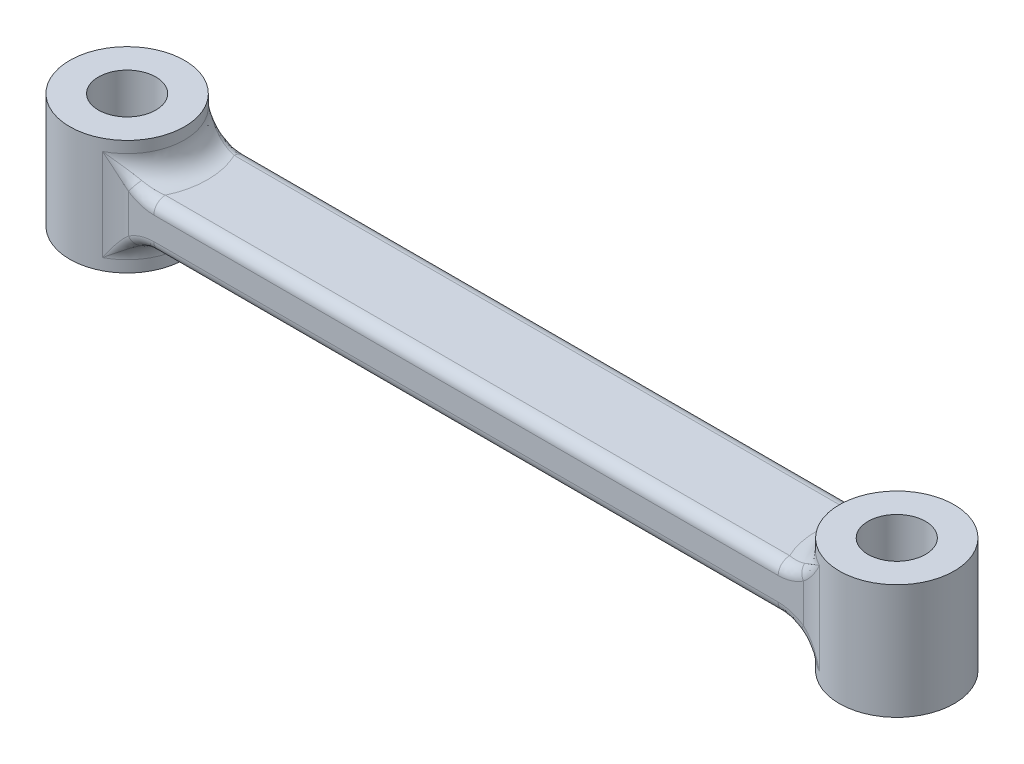
SolidWorks part; units mm, degrees
ref_plane "Front Plane" through (0, 0, 0) normal (0, 0, 1) x (1, 0, 0)
ref_plane "Top Plane" through (0, 0, 0) normal (0, 1, 0) x (1, 0, 0)
ref_plane "Right Plane" through (0, 0, 0) normal (1, 0, 0) x (0, 0, -1)
sketch "Sketch1" plane through (0, 0, 0) normal (0, 1, 0) x (1, 0, 0)
  line L1 (-33.5, 4) -> (33.5, 4)
  line L2 (-33.5, 4) -> (-33.5, -4)
  line L3 (-33.5, -4) -> (33.5, -4)
  line L4 (33.5, 4) -> (33.5, -4)
  line L5 (-33.5, 4) -> (33.5, -4) construction
  line L6 (-33.5, -4) -> (33.5, 4) construction
  point P0 (0, 0)
  dimension "D1" = 67
  dimension "D2" = 8
extrude "Boss-Extrude1" add sketch "Sketch1" along normal mid plane 4
sketch "Sketch2" plane through (0, 0, 0) normal (0, 1, 0) x (1, 0, 0)
  line L0 (-33.5, 4) -> (-33.5, -4) construction
  line L1 (33.5, -4) -> (33.5, 4) construction
  circle A0 centre (-33.5, 0) radius 5
  circle A1 centre (33.5, 0) radius 5
  dimension "D1" = 10
extrude "Boss-Extrude2" add sketch "Sketch2" along normal mid plane 10
sketch "Sketch3" plane through (0, 0, 0) normal (0, 1, 0) x (1, 0, 0)
  circle A0 centre (-33.5, 0) radius 2.5
  circle A1 centre (33.5, 0) radius 2.5
  dimension "D1" = 67
extrude "Cut-Extrude1" cut sketch "Sketch3" along normal through all and the other way through all
fillet "Fillet1" radius 2 4 edges at (28.5, -2, 0) (-28.5, -2, 0) (28.5, 2, 0) (-28.5, 2, 0)
fillet "Fillet2" radius 4 4 edges at (30.5, 0, -4) (-30.5, 0, -4) (30.5, 0, 4) (-30.5, 0, 4)
fillet "Fillet4" radius 1 20 edges at (30.5268, -3.3163, -4.1688) (28.4704, -2.0841, -4) (-30.5268, -3.3163, -4.1688) (-28.7554, -2.1645, -4) (30.5268, 3.3163, -4.1688) (28.7554, 2.1645, -4) (-30.5268, 3.3163, -4.1688) (-28.4704, 2.0841, -4) (-30.5268, -3.3163, 4.1688) (-28.4704, -2.0841, 4) (30.5268, -3.3163, 4.1688) (28.7554, -2.1645, 4) (-30.5268, 3.3163, 4.1688) (-28.7554, 2.1645, 4) (30.5268, 3.3163, 4.1688) (28.4704, 2.0841, 4) (0, -2, -4) (0, 2, -4) (0, -2, 4) (0, 2, 4)
